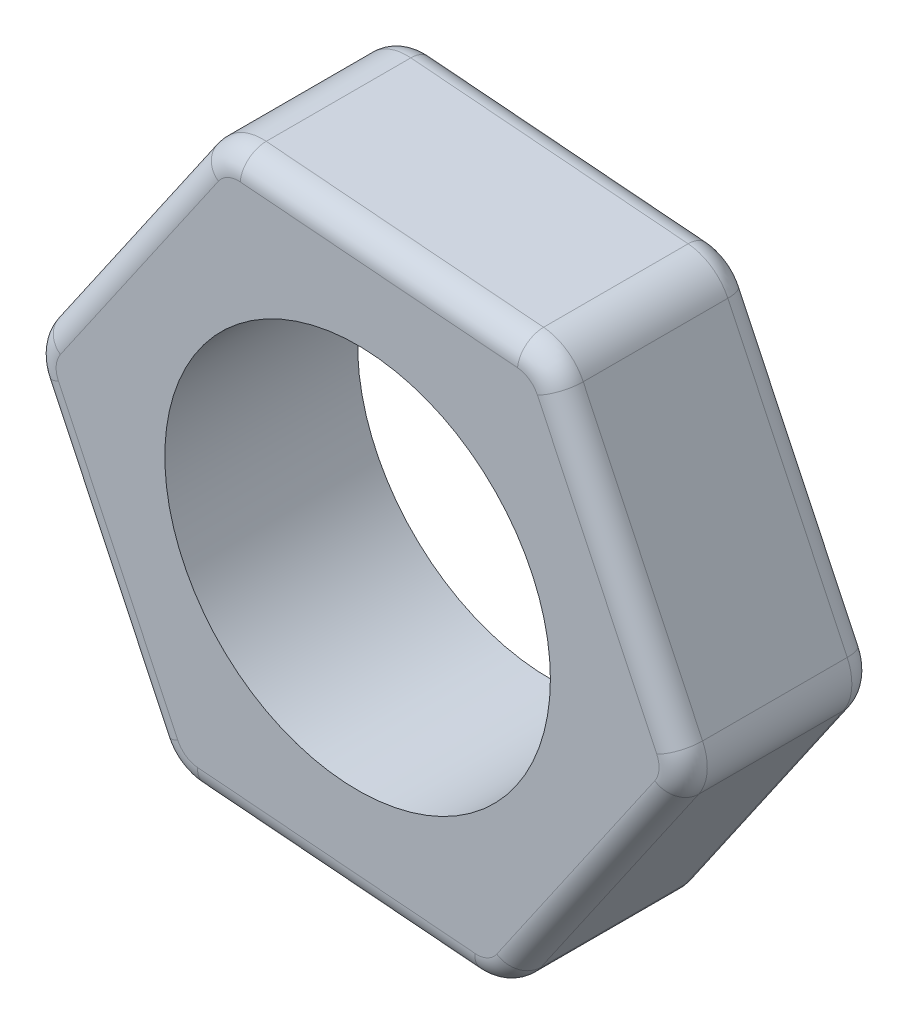
SolidWorks part; units mm, degrees
ref_plane "Front Plane" through (0, 0, 0) normal (0, 0, 1) x (1, 0, 0)
ref_plane "Top Plane" through (0, 0, 0) normal (0, 1, 0) x (1, 0, 0)
ref_plane "Right Plane" through (0, 0, 0) normal (1, 0, 0) x (0, 0, -1)
sketch "Sketch1" plane through (0, 0, 0) normal (0, 0, 1) x (1, 0, 0)
  line L1 (-9.4351, 19.8708) -> (-21.9262, 1.7644)
  line L2 (-21.9262, 1.7644) -> (-12.4911, -18.1064)
  line L3 (-12.4911, -18.1064) -> (9.4351, -19.8708)
  line L4 (9.4351, -19.8708) -> (21.9262, -1.7644)
  line L5 (21.9262, -1.7644) -> (12.4911, 18.1064)
  line L6 (12.4911, 18.1064) -> (-9.4351, 19.8708)
  circle A0 centre (0, 0) radius 12.7
  circle A1 centre (0, 0) radius 19.05 construction
  dimension "D1" = 25.4
  dimension "D3" = 38.1
extrude "Boss-Extrude1" add sketch "Sketch1" along normal mid plane 12.7
fillet "Fillet1" radius 1.5875 12 edges at (-1.528, -18.9886, -6.35) (-17.2086, -8.171, -6.35) (-15.6806, 10.8176, -6.35) (1.528, 18.9886, -6.35) (15.6806, -10.8176, -6.35) (17.2086, 8.171, -6.35) (1.528, 18.9886, 6.35) (-15.6806, 10.8176, 6.35) (-17.2086, -8.171, 6.35) (-1.528, -18.9886, 6.35) (15.6806, -10.8176, 6.35) (17.2086, 8.171, 6.35)
fillet "Fillet2" radius 3.175 18 edges at (12.1862, 17.6645, -5.885) (12.1862, 17.6645, 5.885) (-9.2048, 19.3858, -5.885) (-9.2048, 19.3858, 5.885) (-21.391, 1.7213, -5.885) (-21.391, 1.7213, 5.885) (-12.1862, -17.6645, -5.885) (-12.1862, -17.6645, 5.885) (9.2048, -19.3858, -5.885) (9.2048, -19.3858, 5.885) (21.391, -1.7213, -5.885) (21.391, -1.7213, 5.885) (21.9262, -1.7644, 0) (9.4351, -19.8708, 0) (-12.4911, -18.1064, 0) (-21.9262, 1.7644, 0) (-9.4351, 19.8708, 0) (12.4911, 18.1064, 0)
